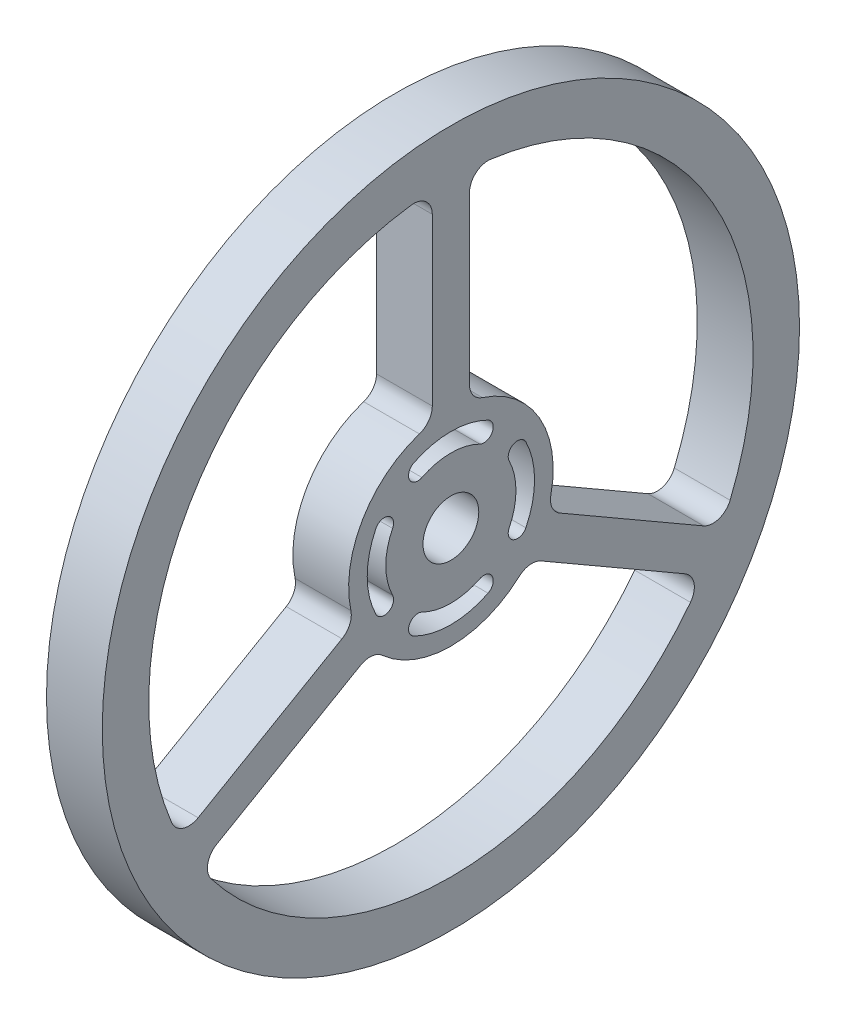
SolidWorks part; units mm, degrees
material "Acrylic (Medium-high impact)"
ref_plane "Front Plane" through (0, 0, 0) normal (0, 0, 1) x (1, 0, 0)
ref_plane "Top Plane" through (0, 0, 0) normal (0, 1, 0) x (1, 0, 0)
ref_plane "Right Plane" through (0, 0, 0) normal (1, 0, 0) x (0, 0, -1)
sketch "Sketch1" plane through (0, 0, 0) normal (1, 0, 0) x (0, 0, -1)
  line L0 (0, 0) -> (0, 37.5) construction
  line L1 (-2, 32.4384) -> (-2, 10.8167)
  line L2 (2, 32.4384) -> (2, 10.8167)
  line L3 (29.0925, -14.4872) -> (10.3675, -3.6763)
  line L4 (27.0925, -17.9513) -> (8.3675, -7.1404)
  line L5 (-27.0925, -17.9513) -> (-8.3675, -7.1404)
  line L6 (-29.0925, -14.4872) -> (-10.3675, -3.6763)
  circle A0 centre (0, 0) radius 37.5
  circle A2 centre (0, 0) radius 32.5
  circle A3 centre (0, 0) radius 3
  circle A4 centre (0, 0) radius 11
  point P23 (0, 0)
  dimension "D1" = 75
  dimension "D3" = 6
  dimension "D6" = 4
  dimension "D2" = 5
  dimension "D4" = 8
  dimension "D5" = 3
extrude "Boss-Extrude1" add sketch "Sketch1" along normal blind 6 contours A2 A0 | A3 A4 | A4 L6 A2 L5 | L0 A4 L2 A2 | A4 L0 A2 L1 | A4 L4 A2 L3 region at (0, 10.6442, -0.9758) region at (0, 21.7092, 1.0009) region at (0, 21.7092, -1.0009) region at (0, 25.7665, -25.7665) region at (0, -10.8546, 18.8007) region at (0, -10.8546, -18.8007)
fillet "Fillet1" radius 2 12 edges at (3, -3.6763, 10.3675) (3, -7.1404, 8.3675) (3, -7.1404, -8.3675) (3, -3.6763, -10.3675) (3, 10.8167, -2) (3, -17.9513, -27.0925) (3, -14.4872, -29.0925) (3, -17.9513, 27.0925) (3, -14.4872, 29.0925) (3, 32.4384, -2) (3, 32.4384, 2) (3, 10.8167, 2)
sketch "Sketch2" plane through (6, 0, 0) normal (1, 0, 0) x (0, 0, -1)
  line L0 (0, 0) -> (0, 11.7058) construction
  line L1 (3.1111, 6.2706) -> (4, 8.0623) construction
  arc A0 (0, 9) -> (4, 8.0623) centre (0, 0) cw
  arc A1 (0, 7) -> (3.1111, 6.2706) centre (0, 0) cw
  circle A2 centre (3.5556, 7.1665) radius 1
  circle A3 centre (-3.5556, 7.1665) radius 1
  arc A4 (0, 7) -> (-3.1111, 6.2706) centre (0, 0) ccw
  arc A5 (0, 9) -> (-4, 8.0623) centre (0, 0) ccw
  dimension "D1" = 9
  dimension "D2" = 4
  dimension "D3" = 2
extrude "Cut-Extrude1" cut sketch "Sketch2" against normal blind 10 contours A0 A5 A3 A4 A1 A2 | A3 | A2 region at (6, 7.8702, 0) region at (6, 7.1665, -3.5556) region at (6, 7.1665, 3.5556)
pattern_circular "CirPattern1" count 4 over 360 about axis through (6, 0, 0) along (1, 0, 0) of "Cut-Extrude1"
